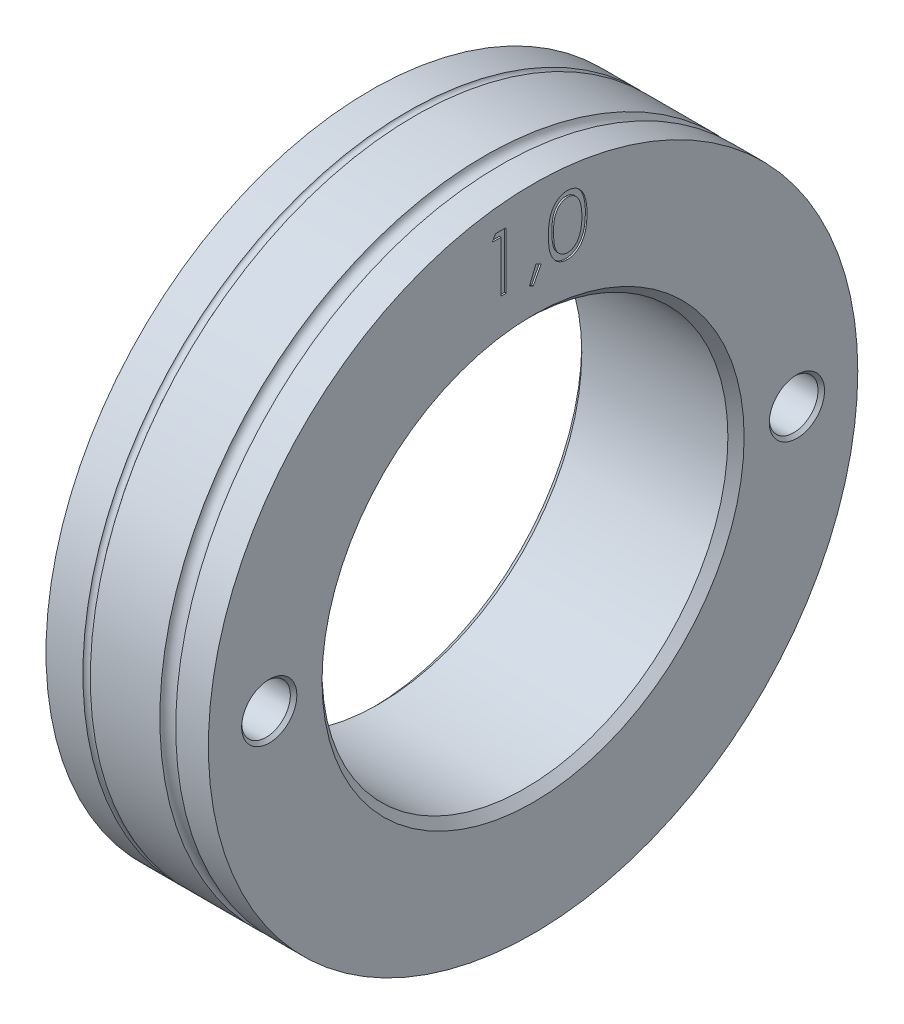
SolidWorks part; units mm, degrees
ref_plane "Спереди" through (0, 0, 0) normal (0, 0, 1) x (1, 0, 0)
ref_plane "Сверху" through (0, 0, 0) normal (0, 1, 0) x (1, 0, 0)
ref_plane "Справа" through (0, 0, 0) normal (1, 0, 0) x (0, 0, -1)
sketch "Эскиз1" plane through (0, 0, 0) normal (0, 0, 1) x (1, 0, 0)
  line L0 (0, 0) -> (-24.5243, 0) construction
  line L1 (0, 12.5) -> (-10, 12.5)
  line L2 (-10, 12.5) -> (-10, 20)
  line L3 (-10, 20) -> (-7.7273, 20)
  line L4 (0, 12.5) -> (0, 20)
  line L5 (0, 20) -> (-2.011, 20)
  line L6 (-2.989, 20) -> (-7.2727, 20)
  arc A0 (-7.7273, 20) -> (-7.2727, 20) centre (-7.5, 20.1041) ccw
  arc A1 (-2.989, 20) -> (-2.011, 20) centre (-2.5, 20.1041) ccw
  dimension "D3" = 0.5
  dimension "D8" = 1
  dimension "D1" = 25
  dimension "D2" = 10
  dimension "D4" = 40
  dimension "D5" = 0.1041
  dimension "D6" = 2.5
  dimension "D7" = 2.5
revolve "Повернуть1" add sketch "Эскиз1" angle 360 about L0
sketch "Эскиз2" plane through (-10, 0, 0) normal (-1, 0, 0) x (0, 0, 1)
  line L0 (0, 0) -> (0, 15) construction
  line L1 (-3.5, 15) -> (3.5, 15) construction
  text T0 "0.5"
  dimension "D1" = 15
  dimension "D2" = 7
extrude "Вырез-Вытянуть1" cut sketch "Эскиз2" against normal blind 0.1
sketch "Эскиз4" plane through (0, 0, 0) normal (1, 0, 0) x (0, 0, -1)
  line L1 (3.5, 15) -> (-3.5, 15) construction
  line L2 (0, 0) -> (0, 15) construction
  line L3 (3.5, 15) -> (-3.5, 15) construction
  line L4 (0, 0) -> (0, 15) construction
  text T0 "1,0"
extrude "Вырез-Вытянуть2" cut sketch "Эскиз4" against normal blind 0.1
sketch "Эскиз5" plane through (-10, 0, 0) normal (-1, 0, 0) x (0, 0, 1)
  line L0 (0, 0) -> (-12.5, 0) construction
  line L1 (-12.5, 0) -> (-20, 0) construction
  line L2 (0, 0) -> (12.5, 0) construction
  line L3 (12.5, 0) -> (20, 0) construction
  circle A0 centre (0, 0) radius 12.5 construction
  circle A1 centre (0, 0) radius 20 construction
  circle A2 centre (-16.25, 0) radius 1.5
  circle A3 centre (16.25, 0) radius 1.5
  dimension "D1" = 3
extrude "Вырез-Вытянуть3" cut sketch "Эскиз5" against normal through all
chamfer "Фаска1" distance 0.5 angle 45 2 edges at (0, 0, -12.5) (-10, 0, -12.5)
chamfer "Фаска2" distance 0.2 angle 45 4 edges at (0, 0, -14.75) (0, 0, 17.75) (-10, 0, 17.75) (-10, 0, -14.75)
equation "\"D7@Эскиз1\"=\"D6@Эскиз1\""
equation "\"Внешний диаметр ролика\" = 40  'Внешний диаметр ролика"
equation "\"Внутренний диаметр ролика\" = 25  'Внутренний диаметр ролика"
equation "\"Ширина ролика\" = 10  'Ширина ролика"
equation "\"Диаметр штифтов ролика\" = 3  'Диаметр штифтов ролика"
equation "\"Пруток_1\" = 0.5  'Пруток_1"
equation "\"Пруток_2\" = 1.0  'Пруток_2"
equation "\"D4@Эскиз1\"=\"Внешний диаметр ролика\""
equation "\"D1@Эскиз1\"=\"Внутренний диаметр ролика\""
equation "\"D2@Эскиз1\"=\"Ширина ролика\""
equation "\"D3@Эскиз1\"=\"Пруток_1\""
equation "\"D8@Эскиз1\"=\"Пруток_2\""
equation "\"D1@Эскиз5\"=\"Диаметр штифтов ролика\""
